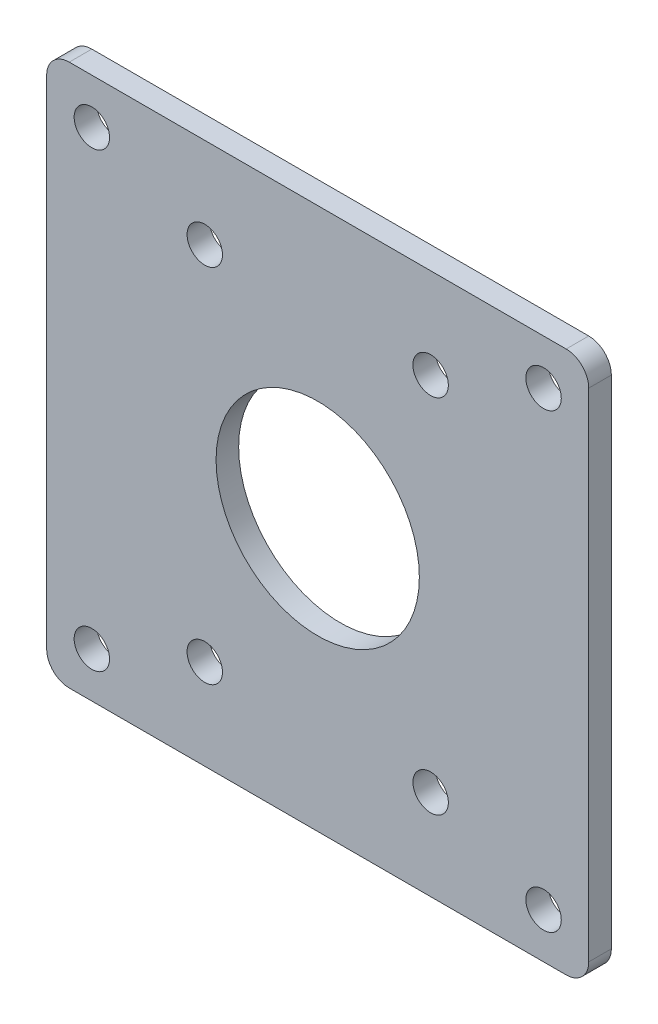
SolidWorks part; units mm, degrees
material "6061-T6 (SS)"
ref_plane "Front Plane" through (0, 0, 0) normal (0, 0, 1) x (1, 0, 0)
ref_plane "Top Plane" through (0, 0, 0) normal (0, 1, 0) x (1, 0, 0)
ref_plane "Right Plane" through (0, 0, 0) normal (1, 0, 0) x (0, 0, -1)
sketch "Sketch1" plane through (0, 0, 0) normal (0, 0, 1) x (1, 0, 0)
  line L9 (-38.1, -38.1) -> (38.1, -38.1)
  line L10 (-38.1, -38.1) -> (-38.1, 38.1)
  line L11 (-38.1, 38.1) -> (38.1, 38.1)
  line L12 (38.1, -38.1) -> (38.1, 38.1)
  line L13 (-38.1, -38.1) -> (38.1, 38.1) construction
  line L14 (-38.1, 38.1) -> (38.1, -38.1) construction
  line L15 (-31.75, -31.75) -> (31.75, -31.75) construction
  line L16 (-31.75, -31.75) -> (-31.75, 31.75) construction
  line L17 (-31.75, 31.75) -> (31.75, 31.75) construction
  line L18 (31.75, -31.75) -> (31.75, 31.75) construction
  line L19 (-31.75, -31.75) -> (31.75, 31.75) construction
  line L20 (-31.75, 31.75) -> (31.75, -31.75) construction
  line L21 (-25.4, -38.1) -> (25.4, -38.1) construction
  line L22 (-25.4, -38.1) -> (-25.4, 38.1) construction
  line L23 (-25.4, 38.1) -> (25.4, 38.1) construction
  line L24 (25.4, -38.1) -> (25.4, 38.1) construction
  line L25 (-25.4, -38.1) -> (25.4, 38.1) construction
  line L26 (-25.4, 38.1) -> (25.4, -38.1) construction
  circle A4 centre (-31.75, 31.75) radius 2.4892
  circle A5 centre (31.75, 31.75) radius 2.4892
  circle A6 centre (31.75, -31.75) radius 2.4892
  circle A7 centre (-31.75, -31.75) radius 2.4892
  circle A8 centre (0, 0) radius 30 construction
  circle A9 centre (0, 0) radius 14.2875
  circle A11 centre (0, 0) radius 9.5758 construction
  circle A12 centre (0, 0) radius 11.5062 construction
  circle A13 centre (-15.875, -25.4) radius 2.4892
  circle A14 centre (15.875, -25.4) radius 2.4892
  circle A15 centre (15.875, 25.4) radius 2.4892
  circle A16 centre (-15.875, 25.4) radius 2.4892
  point P0 (0, 0)
  point P6 (0, 0)
  point P28 (0, 0)
  point P35 (-18.934, 2.0993)
  point P36 (0, 0)
  dimension "D4" = 28.575
  dimension "D3" = 4.9784
  dimension "D5" = 60
  dimension "D7" = 19.1516
  dimension "D8" = 23.0124
  dimension "D10" = 2
  dimension "D11" = 31.75
  dimension "D12" = 50.8
  dimension "D1" = 76.2
  dimension "D2" = 6.35
  dimension "D6" = 50.8
  dimension "D9" = 2
  dimension "D13" = 15.875
  dimension "D14" = 25.4
extrude "Boss-Extrude1" add sketch "Sketch1" along normal blind 3.175
fillet "Fillet1" radius 3.175 4 edges at (38.1, -38.1, 1.5875) (-38.1, -38.1, 1.5875) (-38.1, 38.1, 1.5875) (38.1, 38.1, 1.5875)
